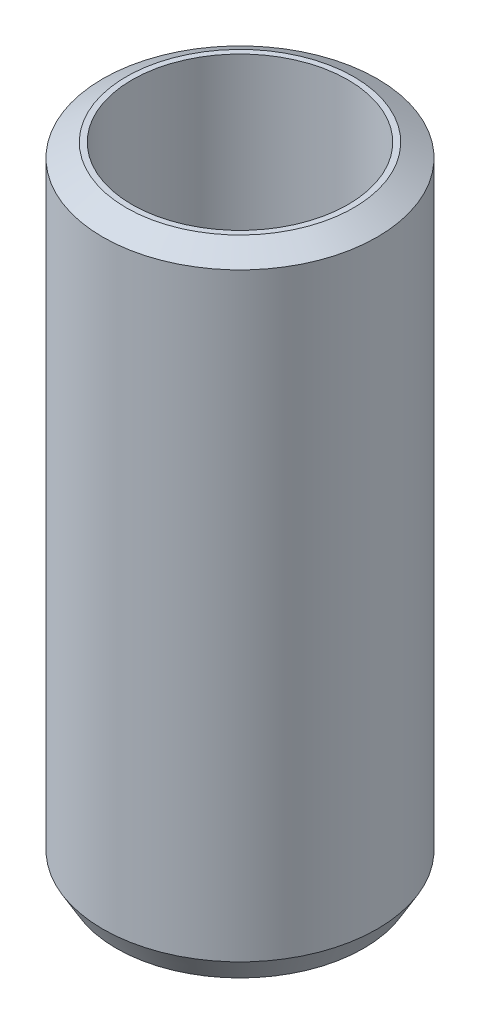
SolidWorks part; units mm, degrees
ref_plane "Front Plane" through (0, 0, 0) normal (0, 0, 1) x (1, 0, 0)
ref_plane "Top Plane" through (0, 0, 0) normal (0, 1, 0) x (1, 0, 0)
ref_plane "Right Plane" through (0, 0, 0) normal (1, 0, 0) x (0, 0, -1)
sketch "Sketch1" plane through (0, 0, 0) normal (0, 1, 0) x (1, 0, 0)
  circle A0 centre (0, 0) radius 40
  dimension "SHAFT_OD" = 80
extrude "Boss-Extrude1" add sketch "Sketch1" along normal blind 185.539
sketch "Sketch2" plane through (0, 0, 0) normal (0, 1, 0) x (1, 0, 0)
  circle A0 centre (0, 0) radius 31.4994
  dimension "BORE_D" = 62.9988
extrude "Cut-Extrude1" cut sketch "Sketch2" along normal through all
chamfer "Chamfer1" distance 3.9614 angle 60 2 edges at (0, 185.539, 40) (0, 0, 40) first distance on face at (0, 185.539, 40) first distance on face at (0, 0, 31.4994)
